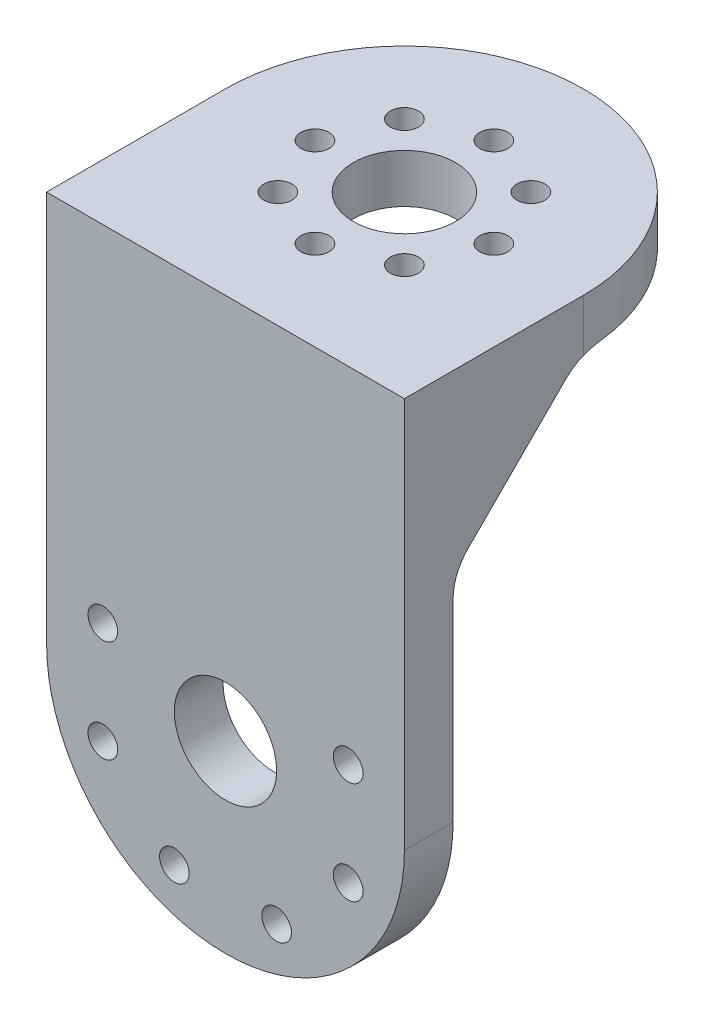
SolidWorks part; units mm, degrees
material "ABS PC"
ref_plane "Front Plane" through (0, 0, 0) normal (0, 0, 1) x (1, 0, 0)
ref_plane "Top Plane" through (0, 0, 0) normal (0, 1, 0) x (1, 0, 0)
ref_plane "Right Plane" through (0, 0, 0) normal (1, 0, 0) x (0, 0, -1)
sketch "Sketch1" plane through (0, 0, 0) normal (0, 1, 0) x (1, 0, 0)
  line L1 (-35, -35) -> (35, -35)
  line L2 (-35, -35) -> (-35, 35)
  line L3 (-35, 35) -> (35, 35)
  line L4 (35, -35) -> (35, 35)
  line L5 (-35, -35) -> (35, 35) construction
  line L6 (-35, 35) -> (35, -35) construction
  point P0 (0, 0)
  dimension "D1" = 70
  dimension "D2" = 70
extrude "Boss-Extrude1" add sketch "Sketch1" along normal blind 9.525 contours L2 L3 L4 L1
sketch "Sketch2" plane through (0, 0, 0) normal (0, -1, 0) x (1, 0, 0)
  circle A0 centre (0, 0) radius 17.5 construction
  circle A1 centre (0, 0) radius 17.5 construction
  circle A2 centre (0, 0) radius 17.5 construction
  circle A3 centre (0, 0) radius 17.5 construction
  circle A4 centre (0, 0) radius 17.5 construction
  circle A5 centre (0, 0) radius 17.5 construction
  circle A6 centre (0, 0) radius 17.5 construction
  circle A7 centre (0, 0) radius 17.5 construction
  point P3 (17.5, 0)
  point P8 (12.3744, -12.3744)
  point P10 (0, -17.5)
  point P12 (-12.3744, -12.3744)
  point P14 (-17.5, 0)
  point P16 (-12.3744, 12.3744)
  point P18 (0, 17.5)
  point P20 (12.3744, 12.3744)
  point P21 (0, 0)
  dimension "D2" = 35
  dimension "D1" = 8
hole_wizard "CBORE for M5 SBHCS1" positions "Sketch3" profile "Sketch4" counterbore size "M5" standard "ANSI Metric" end condition through all
sketch "Sketch3" plane through (0, 0, 0) normal (0, -1, 0) x (-1, 0, 0)
  point P0 (-17.5, 0)
  point P3 (-12.3744, 12.3744)
  point P6 (0, 17.5)
  point P9 (12.3744, 12.3744)
  point P12 (17.5, 0)
  point P15 (12.3744, -12.3744)
  point P18 (0, -17.5)
  point P21 (-12.3744, -12.3744)
sketch "Sketch4" plane through (17.5, 0, 0) normal (1, 0, 0) x (0, 0, -1)
  line L0 (0, 0) -> (0, 9.525)
  line L1 (0, 9.525) -> (2.75, 9.525)
  line L3 (2.75, 9.525) -> (2.75, 2.75)
  line L4 (5.25, 2.75) -> (2.75, 2.75)
  line L5 (5.25, 2.75) -> (5.25, 0.025)
  line L6 (5.25, 0.025) -> (5.275, 0)
  line L7 (5.275, 0) -> (0, 0)
  line L8 (-5.25, 0.025) -> (-5.275, 0) construction
  line L11 (0, -6.35) -> (0, 107.95) construction
  dimension "Thru Hole Dia." = 5.5
  dimension "Thru Hole Depth" = 9.525
  dimension "C'Bore Dia." = 10.5
  dimension "C'Bore Depth" = 2.75
  dimension "Near C'Sink Dia." = 10.55
  dimension "Near C'Sink Angle" = 90
sketch "Sketch5" plane through (0, 0, 0) normal (0, -1, 0) x (1, 0, 0)
  circle A0 centre (0, 0) radius 10
  dimension "D1" = 20
extrude "Cut-Extrude1" cut sketch "Sketch5" against normal through all
sketch "Sketch6" plane through (0, 0, 35) normal (0, 0, 1) x (1, 0, 0)
  line L1 (-35, -102) -> (35, -102)
  line L2 (-35, -102) -> (-35, 0)
  line L3 (-35, 0) -> (35, 0)
  line L4 (35, -102) -> (35, 0)
  line L5 (-35, -102) -> (35, 0) construction
  line L6 (-35, 0) -> (35, -102) construction
  point P0 (0, -51)
  dimension "D1" = 102
extrude "Boss-Extrude2" add sketch "Sketch6" against normal blind 9.525
sketch "Sketch7" plane through (0, 0, 25.475) normal (0, 0, -1) x (-1, 0, 0)
  line L0 (35, -102) -> (-35, -102) construction
  line L1 (0, 5.2388) -> (0, -5.2388) construction
  circle A0 centre (0, -66) radius 10
  point P2 (10, -92)
  point P3 (24, -78)
  point P4 (24, -58)
  point P7 (0, -102)
  point P11 (-24, -58)
  point P12 (-24, -78)
  point P13 (-10, -92)
  dimension "D1" = 20
  dimension "D2" = 8
  dimension "D3" = 20
  dimension "D4" = 26
  dimension "D5" = 10
  dimension "D6" = 24
  dimension "D7" = 10
hole_wizard "CBORE for M5 SHCS1" positions "Sketch14" profile "Sketch16" counterbore size "M5" standard "ANSI Metric" end condition through all
sketch "Sketch14" plane through (0, 0, 25.475) normal (0, 0, -1) x (-1, 0, 0)
  point P0 (-24, -58)
  point P3 (-24, -78)
  point P6 (-10, -92)
  point P9 (10, -92)
  point P12 (24, -78)
  point P15 (24, -58)
sketch "Sketch16" plane through (24, -58, 25.475) normal (1, 0, 0) x (0, 1, 0)
  line L0 (0, 0) -> (0, 9.525)
  line L1 (0, 9.525) -> (2.9, 9.525)
  line L3 (2.9, 9.525) -> (2.9, 5)
  line L4 (2.9, 5) -> (5, 5)
  line L5 (5, 5) -> (5, 0)
  line L7 (5, 0) -> (0, 0)
  line L11 (0, -6.35) -> (0, 107.95) construction
  dimension "Thru Hole Dia." = 5.8
  dimension "Thru Hole Depth" = 9.525
  dimension "C'Bore Dia." = 10
  dimension "C'Bore Depth" = 5
extrude "Cut-Extrude3" cut sketch "Sketch7" against normal blind 9.525 contours A0
sketch "Sketch17" plane through (-35, 0, 0) normal (-1, 0, 0) x (0, 0, 1)
  line L0 (25.475, 0) -> (25.475, -25)
  line L1 (25.475, 0) -> (25.475, -102) construction
  line L2 (25.475, -25) -> (0.475, 0)
  line L3 (25.475, 0) -> (-35, 0) construction
  line L4 (0.475, 0) -> (25.475, 0)
  dimension "D1" = 25
extrude "Boss-Extrude3" add sketch "Sketch17" against normal blind 8
fillet "Fillet1" radius 10 2 edges at (-31, 0, 0.475) (-31, -25, 25.475)
mirror "Mirror1" about plane through (0, 0, 0) normal (1, 0, 0) of "Fillet1", "Boss-Extrude3"
sketch "Sketch18" plane through (0, 0, 35) normal (0, 0, 1) x (1, 0, 0)
  line L0 (35, -92) -> (-35, -92) construction
  line L1 (35, 9.525) -> (35, -102) construction
  line L2 (-35, 9.525) -> (-35, -102) construction
  line L3 (-35, -102) -> (35, -102) construction
  point P6 (15, -92)
  point P7 (-15, -92)
  point P8 (0, -92)
  dimension "D1" = 30
  dimension "D2" = 15
  dimension "D3" = 10
hole_wizard "M4 Clearance Hole1" [suppressed] positions "Sketch19" profile "Sketch21" hole size "M4" standard "ANSI Metric"
sketch "Sketch19" plane through (0, 0, 35) normal (0, 0, 1) x (1, 0, 0)
  point P0 (15, -120)
  point P3 (-15, -120)
sketch "Sketch21" plane through (15, -120, 35) normal (1, 0, 0) x (0, -1, 0)
  line L0 (0, 0) -> (0, 70)
  line L1 (0, 70) -> (2.25, 70)
  line L2 (2.25, 70) -> (2.25, 0)
  line L5 (2.25, 0) -> (0, 0)
  line L11 (0, -6.35) -> (0, 107.95) construction
  dimension "Thru Hole Dia." = 4.5
  dimension "Thru Hole Depth" = 70
fillet "Fillet2" radius 35 4 edges at (-35, 4.7625, -35) (35, 4.7625, -35) (35, -102, 30.2375) (-35, -102, 30.2375)
